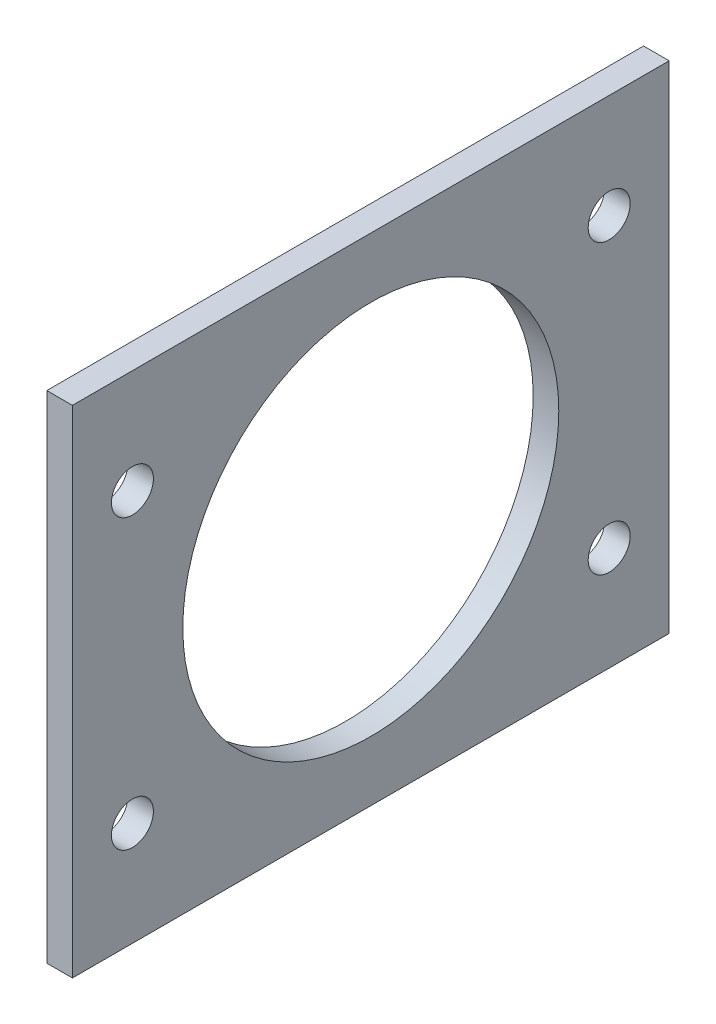
SolidWorks part; units mm, degrees
material "AISI 304"
ref_plane "Front Plane" through (0, 0, 0) normal (0, 0, 1) x (1, 0, 0)
ref_plane "Top Plane" through (0, 0, 0) normal (0, 1, 0) x (1, 0, 0)
ref_plane "Right Plane" through (0, 0, 0) normal (1, 0, 0) x (0, 0, -1)
sketch "Sketch1" plane through (0, 0, 0) normal (1, 0, 0) x (0, 0, -1)
  line L1 (0, 0) -> (74.6, 0)
  line L2 (0, 0) -> (0, 62)
  line L3 (0, 62) -> (74.6, 62)
  line L4 (74.6, 0) -> (74.6, 62)
  dimension "D1" = 74.6
  dimension "D2" = 62
extrude "Boss-Extrude1" add sketch "Sketch1" along normal blind 3.2
sketch "Sketch2" plane through (3.2, 0, 0) normal (1, 0, 0) x (0, 0, -1)
  line L0 (37.3, 62) -> (37.3, 0) construction
  line L1 (74.6, 62) -> (0, 62) construction
  line L2 (0, 0) -> (74.6, 0) construction
  circle A0 centre (37.3, 31) radius 23.5
  point P13 (37.3, 0)
  dimension "D1" = 23.5
extrude "Cut-Extrude1" cut sketch "Sketch2" against normal up to next
sketch "Sketch3" plane through (0, 0, 0) normal (-1, 0, 0) x (0, 0, 1)
  circle A0 centre (-67.1, 13) radius 2.625
  circle A1 centre (-67.1, 49) radius 2.625
  circle A2 centre (-7.5, 13) radius 2.625
  circle A3 centre (-7.5, 49) radius 2.625
extrude "Cut-Extrude2" cut sketch "Sketch3" against normal up to next
